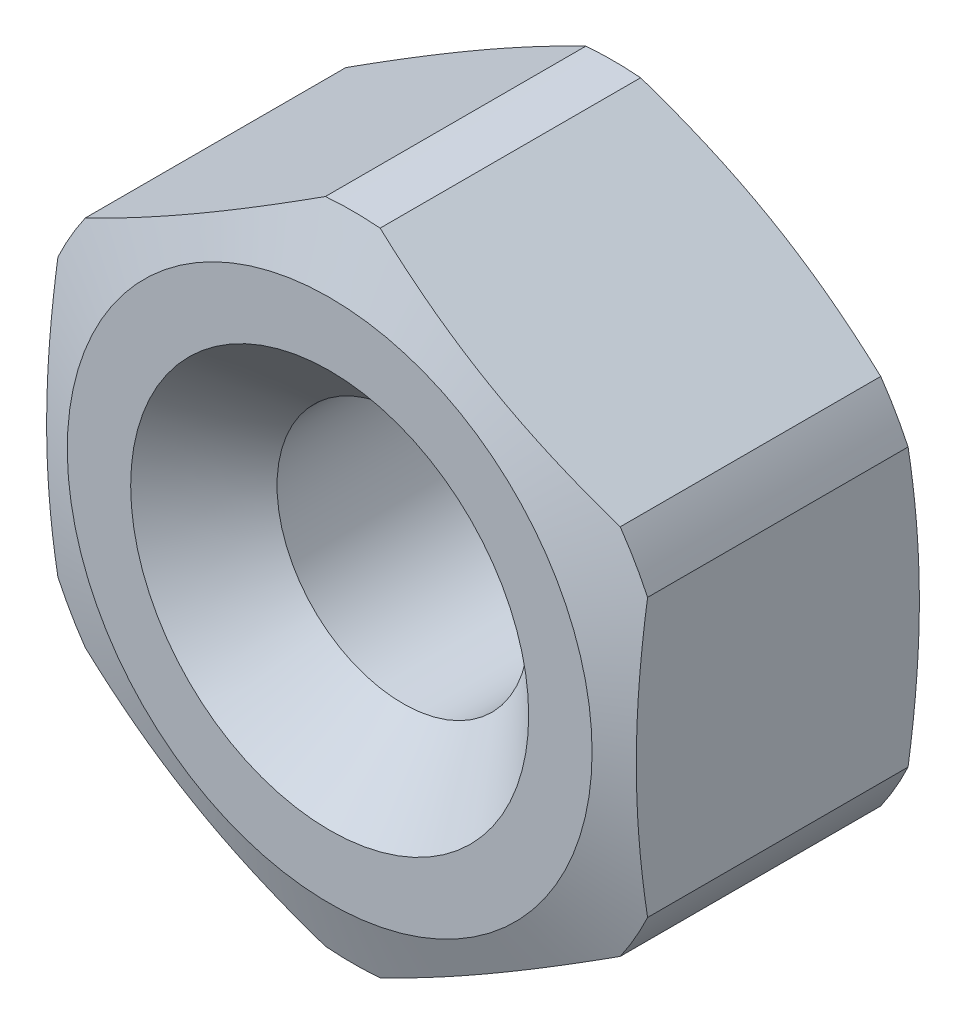
SolidWorks part; units mm, degrees
material "AISI 1020"
ref_plane "Спереди" through (0, 0, 0) normal (0, 0, 1) x (1, 0, 0)
ref_plane "Сверху" through (0, 0, 0) normal (0, 1, 0) x (1, 0, 0)
ref_plane "Справа" through (0, 0, 0) normal (1, 0, 0) x (0, 0, -1)
sketch "Эскиз1" plane through (0, 0, 0) normal (1, 0, 0) x (0, 0, -1)
  line L0 (-152.7402, 0) -> (7484.2692, 0) construction
  line L1 (-1.359, 2.134) -> (1.359, 2.134)
  line L5 (2.2087, 5.525) -> (-2.2087, 5.525)
  line L6 (-2.2087, 5.525) -> (-2.6, 4.45)
  line L7 (-2.6, 4.45) -> (-2.6, 3.375)
  line L8 (-2.6, 3.375) -> (-1.359, 2.134)
  line L9 (0, -152.7402) -> (0, 7484.2692) construction
  line L10 (0, 3) -> (0, -3) construction
  line L11 (-0.5, 3) -> (0.5, 3) construction
  line L12 (0.5, 3) -> (0, 2.134) construction
  line L13 (0, 2.134) -> (-0.5, 3) construction
  line L14 (2.2087, 5.525) -> (2.6, 4.45)
  line L15 (2.6, 4.45) -> (2.6, 3.375)
  line L16 (2.6, 3.375) -> (1.359, 2.134)
  point P8 (0, 0)
  point P16 (0, 3)
  point P20 (0, 5.525)
  point P23 (0, 2.134)
  dimension "D1" = 20
  dimension "_e" = 11.05
  dimension "_dw" = 8.9
  dimension "D2" = 45
  dimension "_da" = 6.75
  dimension "_D" = 6
  dimension "_pa" = 1
  dimension "_m" = 5.2
revolve "Повернуть1" add sketch "Эскиз1" angle 360 about L0
sketch "Эскиз2" plane through (0, 0, 2.6) normal (0, 0, 1) x (1, 0, 0)
  line L1 (0, -5.7735) -> (5, -2.8868)
  line L2 (5, -2.8868) -> (5, 2.8868)
  line L3 (5, 2.8868) -> (0, 5.7735)
  line L4 (0, 5.7735) -> (-5, 2.8868)
  line L5 (-5, 2.8868) -> (-5, -2.8868)
  line L6 (-5, -2.8868) -> (0, -5.7735)
  circle A0 centre (0, 0) radius 5 construction
  dimension "_S" = 10
extrude "Вырез-Вытянуть1" cut sketch "Эскиз2" against normal through all flip side to cut
